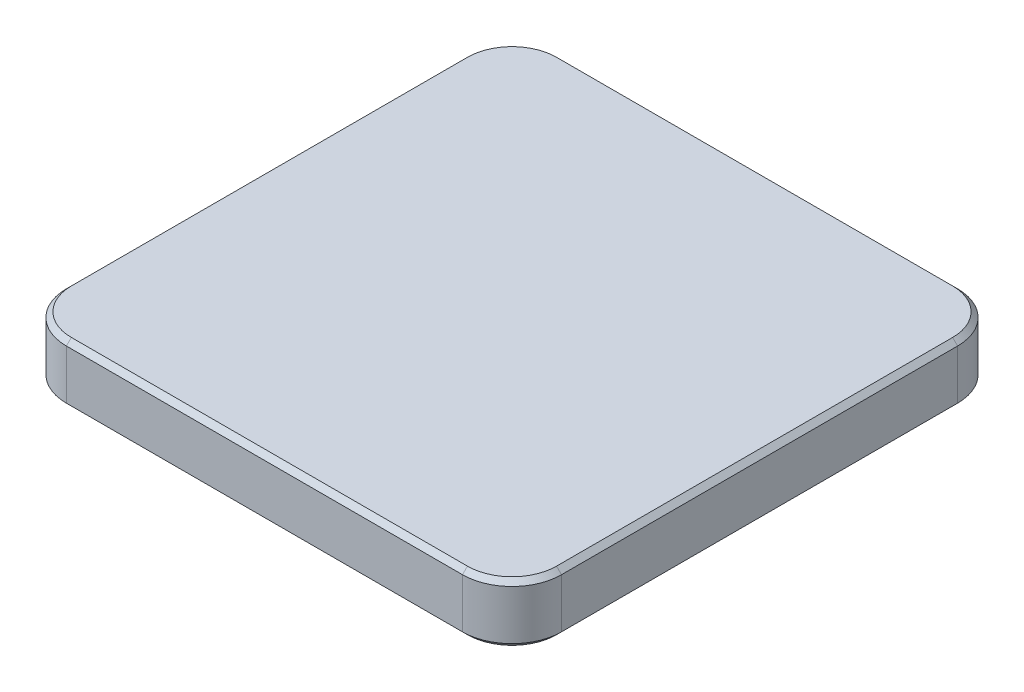
SolidWorks part; units mm, degrees
ref_plane "Alzado" through (0, 0, 0) normal (0, 0, 1) x (1, 0, 0)
ref_plane "Planta" through (0, 0, 0) normal (0, 1, 0) x (1, 0, 0)
ref_plane "Vista lateral" through (0, 0, 0) normal (1, 0, 0) x (0, 0, -1)
sketch "Croquis1" plane through (0, 0, 0) normal (0, 1, 0) x (1, 0, 0)
  line L1 (50, -50) -> (-50, -50)
  line L2 (50, -50) -> (50, 50)
  line L3 (50, 50) -> (-50, 50)
  line L4 (-50, -50) -> (-50, 50)
  line L5 (50, -50) -> (-50, 50) construction
  line L6 (50, 50) -> (-50, -50) construction
  point P0 (0, 0)
  dimension "D1" = 100
extrude "Saliente-Extruir2" add sketch "Croquis1" along normal blind 12
chamfer "Chaflán1" distance 1 angle 45 8 edges at (0, 0, 50) (50, 0, 0) (-50, 0, 0) (0, 0, -50) (50, 12, 0) (0, 12, -50) (-50, 12, 0) (0, 12, 50)
fillet "Redondeo1" radius 10 4 edges at (50, 6, 50) (-50, 6, 50) (-50, 6, -50) (50, 6, -50)
chamfer "Chaflán2" distance 1 angle 45 8 edges at (-47.0711, 0, 47.0711) (-47.0711, 12, 47.0711) (-47.0711, 0, -47.0711) (-47.0711, 12, -47.0711) (47.0711, 0, -47.0711) (47.0711, 0, 47.0711) (47.0711, 12, 47.0711) (47.0711, 12, -47.0711)
